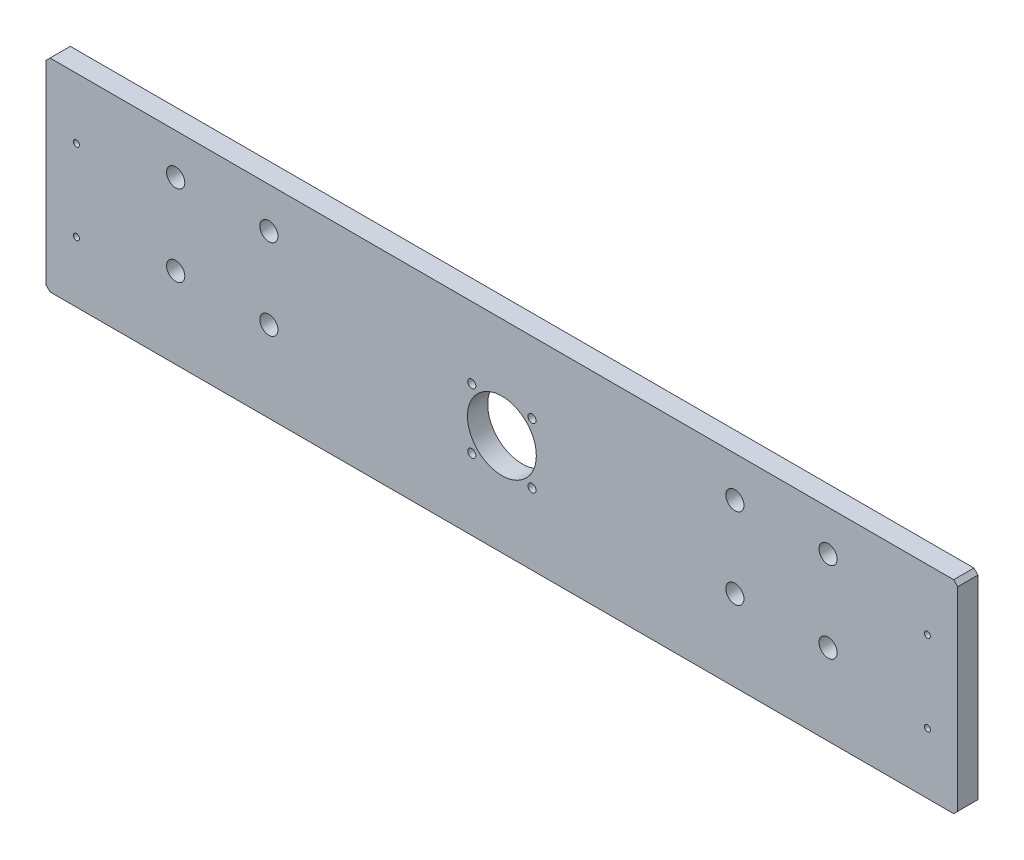
SolidWorks part; units mm, degrees
ref_plane "Piano frontale" through (0, 0, 0) normal (0, 0, 1) x (1, 0, 0)
ref_plane "Piano superiore" through (0, 0, 0) normal (0, 1, 0) x (1, 0, 0)
ref_plane "Piano destro" through (0, 0, 0) normal (1, 0, 0) x (0, 0, -1)
sketch "Schizzo1" plane through (0, 0, 0) normal (0, 0, 1) x (1, 0, 0)
  line L0 (225, 100) -> (225, 0) construction
  line L1 (2, 0) -> (448, 0)
  line L2 (0, 2) -> (0, 98)
  line L3 (2, 100) -> (448, 100)
  line L4 (450, 2) -> (450, 98)
  line L5 (87, 100) -> (87, 0) construction
  line L7 (225, 50) -> (243.5099, 50) construction
  line L9 (225, 50) -> (205.51, 69.49) construction
  line L21 (0, 98) -> (2, 100)
  line L22 (2, 0) -> (0, 2)
  line L23 (448, 0) -> (450, 2)
  line L24 (448, 100) -> (450, 98)
  circle A0 centre (225, 50) radius 17
  circle A1 centre (225, 50) radius 21 construction
  circle A2 centre (239.8492, 64.8492) radius 2
  circle A3 centre (239.8492, 35.1508) radius 2
  circle A4 centre (210.1508, 35.1508) radius 2
  circle A5 centre (386, 40) radius 4.5
  circle A6 centre (386, 80) radius 4.5
  circle A7 centre (340, 40) radius 4.5
  circle A8 centre (340, 80) radius 4.5
  circle A9 centre (435, 70) radius 1.5
  circle A10 centre (435, 30) radius 1.5
  circle A11 centre (15, 30) radius 1.5
  circle A13 centre (210.1508, 64.8492) radius 2
  circle A18 centre (15, 70) radius 1.5
  circle A29 centre (110, 80) radius 4.5
  circle A30 centre (110, 40) radius 4.5
  circle A32 centre (64, 80) radius 4.5
  circle A33 centre (64, 40) radius 4.5
  point P0 (0, 0)
  point P1 (450, 100)
  point P2 (0, 100)
  point P3 (450, 0)
  point P9 (210.1508, 64.8492)
  point P13 (210.1508, 64.8492)
  dimension "D4" = 34
  dimension "D10" = 23
  dimension "D15" = 3
  dimension "D17" = 4
  dimension "D8" = 45
  dimension "D5" = 42
  dimension "D9" = 64
  dimension "D11" = 9
  dimension "D1" = 100
  dimension "D2" = 450
  dimension "D6" = 20
  dimension "D7" = 40
  dimension "D14" = 30
  dimension "D16" = 15
extrude "Boss-Extrude1" add sketch "Schizzo1" against normal blind 10
